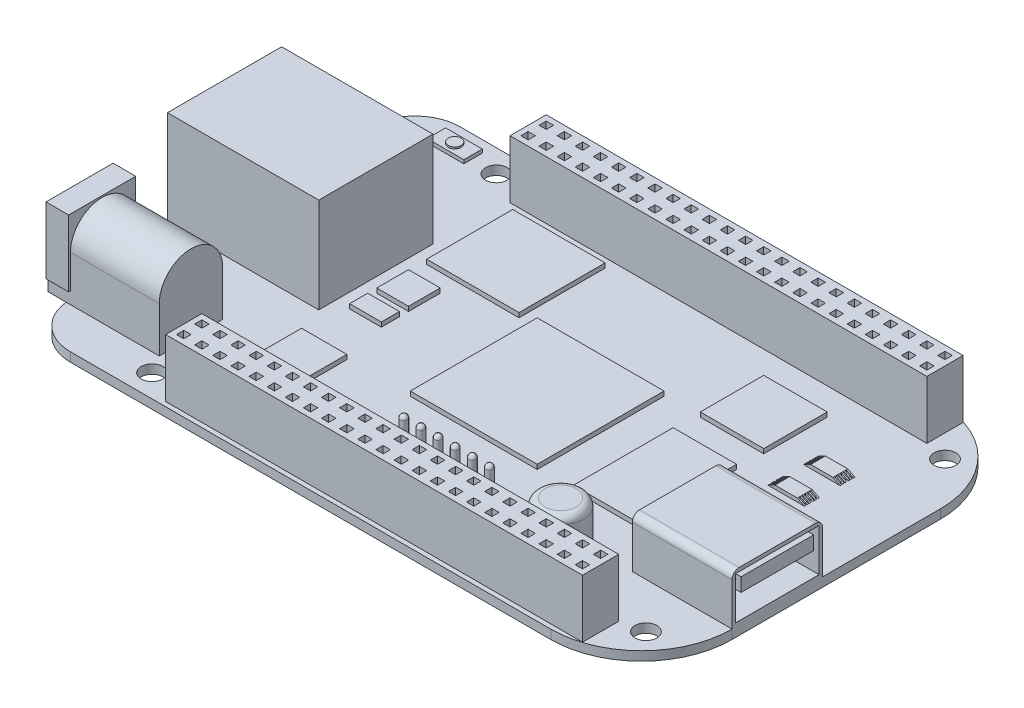
SolidWorks part; units mm, degrees
material "ABS"
ref_plane "Front Plane" through (0, 0, 0) normal (0, 0, 1) x (1, 0, 0)
ref_plane "Top Plane" through (0, 0, 0) normal (0, 1, 0) x (1, 0, 0)
ref_plane "Right Plane" through (0, 0, 0) normal (1, 0, 0) x (0, 0, -1)
sketch "Sketch1" plane through (0, 0, 0) normal (0, 1, 0) x (1, 0, 0)
  line L1 (-12.7, 0) -> (-80.01, 0)
  line L2 (0, 12.7) -> (0, 41.91)
  line L3 (-12.7, 54.61) -> (-80.01, 54.61)
  line L4 (-86.36, 6.35) -> (-86.36, 48.26)
  arc A0 (0, 12.7) -> (-12.7, 0) centre (-12.7, 12.7) cw
  arc A1 (0, 41.91) -> (-12.7, 54.61) centre (-12.7, 41.91) ccw
  arc A2 (-86.36, 6.35) -> (-80.01, 0) centre (-80.01, 6.35) ccw
  arc A3 (-86.36, 48.26) -> (-80.01, 54.61) centre (-80.01, 48.26) cw
  point P7 (0, 0)
  point P10 (0, 54.61)
  point P13 (-86.36, 0)
  dimension "D3" = 12.7
  dimension "D4" = 6.35
  dimension "D1" = 86.36
  dimension "D2" = 54.61
extrude "Boss-Extrude1" add sketch "Sketch1" along normal blind 1.27
sketch "Sketch2" plane through (0, 1.27, 0) normal (0, 1, 0) x (1, 0, 0)
  line L0 (-80.01, 0) -> (-12.7, 0) construction
  line L2 (-71.755, 51.435) -> (-71.755, 3.175) construction
  line L3 (-86.36, 48.26) -> (-86.36, 6.35) construction
  line L4 (-5.715, 48.26) -> (-5.715, 6.35) construction
  circle A0 centre (-71.755, 51.435) radius 1.524
  circle A1 centre (-71.755, 3.175) radius 1.524
  circle A2 centre (-5.715, 48.26) radius 1.524
  circle A3 centre (-5.715, 6.35) radius 1.524
  dimension "D7" = 3.048
  dimension "D1" = 48.26
  dimension "D2" = 41.91
  dimension "D3" = 6.35
  dimension "D4" = 14.605
  dimension "D5" = 80.645
  dimension "D6" = 3.175
extrude "Cut-Extrude1" cut sketch "Sketch2" along direction (0, -1, 0) on the side against the normal up to surface (1.27 mm away) up to face at (-44.4387, 0, -27.305)
sketch "Sketch3" plane through (0, 1.27, 0) normal (0, 1, 0) x (1, 0, 0)
  line L0 (-10.16, 48.895) -> (-10.16, 50.165) construction
  line L1 (-67.31, 53.975) -> (-8.89, 53.975)
  line L2 (-67.31, 53.975) -> (-67.31, 48.895)
  line L3 (-67.31, 48.895) -> (-8.89, 48.895)
  line L4 (-8.89, 53.975) -> (-8.89, 48.895)
  line L5 (-86.36, 27.305) -> (0, 27.305) construction
  line L6 (0, 12.7) -> (0, 41.91) construction
  line L7 (-66.548, 4.953) -> (-66.548, 3.937)
  line L8 (-66.548, 4.953) -> (-65.532, 4.953)
  line L9 (-10.16, 50.165) -> (-10.16, 52.705) construction
  line L10 (-10.16, 52.705) -> (-10.16, 53.975) construction
  line L11 (-13.208, 52.197) -> (-12.192, 52.197)
  line L12 (-10.668, 53.213) -> (-9.652, 53.213)
  line L13 (-10.668, 53.213) -> (-10.668, 52.197)
  line L14 (-10.668, 52.197) -> (-9.652, 52.197)
  line L15 (-9.652, 53.213) -> (-9.652, 52.197)
  line L16 (-10.668, 53.213) -> (-9.652, 52.197) construction
  line L17 (-10.668, 52.197) -> (-9.652, 53.213) construction
  line L18 (-10.668, 49.657) -> (-9.652, 49.657)
  line L19 (-10.668, 49.657) -> (-10.668, 50.673)
  line L20 (-10.668, 50.673) -> (-9.652, 50.673)
  line L21 (-9.652, 49.657) -> (-9.652, 50.673)
  line L22 (-10.668, 49.657) -> (-9.652, 50.673) construction
  line L23 (-10.668, 50.673) -> (-9.652, 49.657) construction
  line L24 (-13.208, 53.213) -> (-13.208, 52.197)
  line L25 (-13.208, 53.213) -> (-12.192, 53.213)
  line L26 (-12.192, 53.213) -> (-12.192, 52.197)
  line L27 (-13.208, 50.673) -> (-12.192, 50.673)
  line L28 (-12.192, 49.657) -> (-12.192, 50.673)
  line L29 (-13.208, 49.657) -> (-12.192, 49.657)
  line L30 (-13.208, 49.657) -> (-13.208, 50.673)
  line L31 (-15.748, 52.197) -> (-14.732, 52.197)
  line L32 (-15.748, 53.213) -> (-15.748, 52.197)
  line L33 (-15.748, 53.213) -> (-14.732, 53.213)
  line L34 (-14.732, 53.213) -> (-14.732, 52.197)
  line L35 (-15.748, 50.673) -> (-14.732, 50.673)
  line L36 (-14.732, 49.657) -> (-14.732, 50.673)
  line L37 (-15.748, 49.657) -> (-14.732, 49.657)
  line L38 (-15.748, 49.657) -> (-15.748, 50.673)
  line L39 (-18.288, 52.197) -> (-17.272, 52.197)
  line L40 (-18.288, 53.213) -> (-18.288, 52.197)
  line L41 (-18.288, 53.213) -> (-17.272, 53.213)
  line L42 (-17.272, 53.213) -> (-17.272, 52.197)
  line L43 (-18.288, 50.673) -> (-17.272, 50.673)
  line L44 (-17.272, 49.657) -> (-17.272, 50.673)
  line L45 (-18.288, 49.657) -> (-17.272, 49.657)
  line L46 (-18.288, 49.657) -> (-18.288, 50.673)
  line L47 (-20.828, 52.197) -> (-19.812, 52.197)
  line L48 (-20.828, 53.213) -> (-20.828, 52.197)
  line L49 (-20.828, 53.213) -> (-19.812, 53.213)
  line L50 (-19.812, 53.213) -> (-19.812, 52.197)
  line L51 (-20.828, 50.673) -> (-19.812, 50.673)
  line L52 (-19.812, 49.657) -> (-19.812, 50.673)
  line L53 (-20.828, 49.657) -> (-19.812, 49.657)
  line L54 (-20.828, 49.657) -> (-20.828, 50.673)
  line L55 (-23.368, 52.197) -> (-22.352, 52.197)
  line L56 (-23.368, 53.213) -> (-23.368, 52.197)
  line L57 (-23.368, 53.213) -> (-22.352, 53.213)
  line L58 (-22.352, 53.213) -> (-22.352, 52.197)
  line L59 (-23.368, 50.673) -> (-22.352, 50.673)
  line L60 (-22.352, 49.657) -> (-22.352, 50.673)
  line L61 (-23.368, 49.657) -> (-22.352, 49.657)
  line L62 (-23.368, 49.657) -> (-23.368, 50.673)
  line L63 (-25.908, 52.197) -> (-24.892, 52.197)
  line L64 (-25.908, 53.213) -> (-25.908, 52.197)
  line L65 (-25.908, 53.213) -> (-24.892, 53.213)
  line L66 (-24.892, 53.213) -> (-24.892, 52.197)
  line L67 (-25.908, 50.673) -> (-24.892, 50.673)
  line L68 (-24.892, 49.657) -> (-24.892, 50.673)
  line L69 (-25.908, 49.657) -> (-24.892, 49.657)
  line L70 (-25.908, 49.657) -> (-25.908, 50.673)
  line L71 (-28.448, 52.197) -> (-27.432, 52.197)
  line L72 (-28.448, 53.213) -> (-28.448, 52.197)
  line L73 (-28.448, 53.213) -> (-27.432, 53.213)
  line L74 (-27.432, 53.213) -> (-27.432, 52.197)
  line L75 (-28.448, 50.673) -> (-27.432, 50.673)
  line L76 (-27.432, 49.657) -> (-27.432, 50.673)
  line L77 (-28.448, 49.657) -> (-27.432, 49.657)
  line L78 (-28.448, 49.657) -> (-28.448, 50.673)
  line L79 (-30.988, 52.197) -> (-29.972, 52.197)
  line L80 (-30.988, 53.213) -> (-30.988, 52.197)
  line L81 (-30.988, 53.213) -> (-29.972, 53.213)
  line L82 (-29.972, 53.213) -> (-29.972, 52.197)
  line L83 (-30.988, 50.673) -> (-29.972, 50.673)
  line L84 (-29.972, 49.657) -> (-29.972, 50.673)
  line L85 (-30.988, 49.657) -> (-29.972, 49.657)
  line L86 (-30.988, 49.657) -> (-30.988, 50.673)
  line L87 (-33.528, 52.197) -> (-32.512, 52.197)
  line L88 (-33.528, 53.213) -> (-33.528, 52.197)
  line L89 (-33.528, 53.213) -> (-32.512, 53.213)
  line L90 (-32.512, 53.213) -> (-32.512, 52.197)
  line L91 (-33.528, 50.673) -> (-32.512, 50.673)
  line L92 (-32.512, 49.657) -> (-32.512, 50.673)
  line L93 (-33.528, 49.657) -> (-32.512, 49.657)
  line L94 (-33.528, 49.657) -> (-33.528, 50.673)
  line L95 (-36.068, 52.197) -> (-35.052, 52.197)
  line L96 (-36.068, 53.213) -> (-36.068, 52.197)
  line L97 (-36.068, 53.213) -> (-35.052, 53.213)
  line L98 (-35.052, 53.213) -> (-35.052, 52.197)
  line L99 (-36.068, 50.673) -> (-35.052, 50.673)
  line L100 (-35.052, 49.657) -> (-35.052, 50.673)
  line L101 (-36.068, 49.657) -> (-35.052, 49.657)
  line L102 (-36.068, 49.657) -> (-36.068, 50.673)
  line L103 (-38.608, 52.197) -> (-37.592, 52.197)
  line L104 (-38.608, 53.213) -> (-38.608, 52.197)
  line L105 (-38.608, 53.213) -> (-37.592, 53.213)
  line L106 (-37.592, 53.213) -> (-37.592, 52.197)
  line L107 (-38.608, 50.673) -> (-37.592, 50.673)
  line L108 (-37.592, 49.657) -> (-37.592, 50.673)
  line L109 (-38.608, 49.657) -> (-37.592, 49.657)
  line L110 (-38.608, 49.657) -> (-38.608, 50.673)
  line L111 (-41.148, 52.197) -> (-40.132, 52.197)
  line L112 (-41.148, 53.213) -> (-41.148, 52.197)
  line L113 (-41.148, 53.213) -> (-40.132, 53.213)
  line L114 (-40.132, 53.213) -> (-40.132, 52.197)
  line L115 (-41.148, 50.673) -> (-40.132, 50.673)
  line L116 (-40.132, 49.657) -> (-40.132, 50.673)
  line L117 (-41.148, 49.657) -> (-40.132, 49.657)
  line L118 (-41.148, 49.657) -> (-41.148, 50.673)
  line L119 (-43.688, 52.197) -> (-42.672, 52.197)
  line L120 (-43.688, 53.213) -> (-43.688, 52.197)
  line L121 (-43.688, 53.213) -> (-42.672, 53.213)
  line L122 (-42.672, 53.213) -> (-42.672, 52.197)
  line L123 (-43.688, 50.673) -> (-42.672, 50.673)
  line L124 (-42.672, 49.657) -> (-42.672, 50.673)
  line L125 (-43.688, 49.657) -> (-42.672, 49.657)
  line L126 (-43.688, 49.657) -> (-43.688, 50.673)
  line L127 (-46.228, 52.197) -> (-45.212, 52.197)
  line L128 (-46.228, 53.213) -> (-46.228, 52.197)
  line L129 (-46.228, 53.213) -> (-45.212, 53.213)
  line L130 (-45.212, 53.213) -> (-45.212, 52.197)
  line L131 (-46.228, 50.673) -> (-45.212, 50.673)
  line L132 (-45.212, 49.657) -> (-45.212, 50.673)
  line L133 (-46.228, 49.657) -> (-45.212, 49.657)
  line L134 (-46.228, 49.657) -> (-46.228, 50.673)
  line L135 (-48.768, 52.197) -> (-47.752, 52.197)
  line L136 (-48.768, 53.213) -> (-48.768, 52.197)
  line L137 (-48.768, 53.213) -> (-47.752, 53.213)
  line L138 (-47.752, 53.213) -> (-47.752, 52.197)
  line L139 (-48.768, 50.673) -> (-47.752, 50.673)
  line L140 (-47.752, 49.657) -> (-47.752, 50.673)
  line L141 (-48.768, 49.657) -> (-47.752, 49.657)
  line L142 (-48.768, 49.657) -> (-48.768, 50.673)
  line L143 (-51.308, 52.197) -> (-50.292, 52.197)
  line L144 (-51.308, 53.213) -> (-51.308, 52.197)
  line L145 (-51.308, 53.213) -> (-50.292, 53.213)
  line L146 (-50.292, 53.213) -> (-50.292, 52.197)
  line L147 (-51.308, 50.673) -> (-50.292, 50.673)
  line L148 (-50.292, 49.657) -> (-50.292, 50.673)
  line L149 (-51.308, 49.657) -> (-50.292, 49.657)
  line L150 (-51.308, 49.657) -> (-51.308, 50.673)
  line L151 (-53.848, 52.197) -> (-52.832, 52.197)
  line L152 (-53.848, 53.213) -> (-53.848, 52.197)
  line L153 (-53.848, 53.213) -> (-52.832, 53.213)
  line L154 (-52.832, 53.213) -> (-52.832, 52.197)
  line L155 (-53.848, 50.673) -> (-52.832, 50.673)
  line L156 (-52.832, 49.657) -> (-52.832, 50.673)
  line L157 (-53.848, 49.657) -> (-52.832, 49.657)
  line L158 (-53.848, 49.657) -> (-53.848, 50.673)
  line L159 (-56.388, 52.197) -> (-55.372, 52.197)
  line L160 (-56.388, 53.213) -> (-56.388, 52.197)
  line L161 (-56.388, 53.213) -> (-55.372, 53.213)
  line L162 (-55.372, 53.213) -> (-55.372, 52.197)
  line L163 (-56.388, 50.673) -> (-55.372, 50.673)
  line L164 (-55.372, 49.657) -> (-55.372, 50.673)
  line L165 (-56.388, 49.657) -> (-55.372, 49.657)
  line L166 (-56.388, 49.657) -> (-56.388, 50.673)
  line L167 (-58.928, 52.197) -> (-57.912, 52.197)
  line L168 (-58.928, 53.213) -> (-58.928, 52.197)
  line L169 (-58.928, 53.213) -> (-57.912, 53.213)
  line L170 (-57.912, 53.213) -> (-57.912, 52.197)
  line L171 (-58.928, 50.673) -> (-57.912, 50.673)
  line L172 (-57.912, 49.657) -> (-57.912, 50.673)
  line L173 (-58.928, 49.657) -> (-57.912, 49.657)
  line L174 (-58.928, 49.657) -> (-58.928, 50.673)
  line L175 (-61.468, 52.197) -> (-60.452, 52.197)
  line L176 (-61.468, 53.213) -> (-61.468, 52.197)
  line L177 (-61.468, 53.213) -> (-60.452, 53.213)
  line L178 (-60.452, 53.213) -> (-60.452, 52.197)
  line L179 (-61.468, 50.673) -> (-60.452, 50.673)
  line L180 (-60.452, 49.657) -> (-60.452, 50.673)
  line L181 (-61.468, 49.657) -> (-60.452, 49.657)
  line L182 (-61.468, 49.657) -> (-61.468, 50.673)
  line L183 (-64.008, 52.197) -> (-62.992, 52.197)
  line L184 (-64.008, 53.213) -> (-64.008, 52.197)
  line L185 (-64.008, 53.213) -> (-62.992, 53.213)
  line L186 (-62.992, 53.213) -> (-62.992, 52.197)
  line L187 (-64.008, 50.673) -> (-62.992, 50.673)
  line L188 (-62.992, 49.657) -> (-62.992, 50.673)
  line L189 (-64.008, 49.657) -> (-62.992, 49.657)
  line L190 (-64.008, 49.657) -> (-64.008, 50.673)
  line L191 (-66.548, 52.197) -> (-65.532, 52.197)
  line L192 (-66.548, 53.213) -> (-66.548, 52.197)
  line L193 (-66.548, 53.213) -> (-65.532, 53.213)
  line L194 (-65.532, 53.213) -> (-65.532, 52.197)
  line L195 (-66.548, 50.673) -> (-65.532, 50.673)
  line L196 (-65.532, 49.657) -> (-65.532, 50.673)
  line L197 (-66.548, 49.657) -> (-65.532, 49.657)
  line L198 (-66.548, 49.657) -> (-66.548, 50.673)
  line L199 (-66.548, 49.657) -> (-65.532, 50.673) construction
  line L200 (-86.36, 48.26) -> (-86.36, 6.35) construction
  line L201 (-65.532, 4.953) -> (-65.532, 3.937)
  line L202 (-12.7, 54.61) -> (-80.01, 54.61) construction
  line L203 (-66.548, 3.937) -> (-65.532, 3.937)
  line L204 (-65.532, 1.397) -> (-65.532, 2.413)
  line L205 (-66.548, 1.397) -> (-65.532, 1.397)
  line L206 (-66.548, 1.397) -> (-66.548, 2.413)
  line L207 (-66.548, 2.413) -> (-65.532, 2.413)
  line L208 (-64.008, 4.953) -> (-64.008, 3.937)
  line L209 (-64.008, 4.953) -> (-62.992, 4.953)
  line L210 (-62.992, 4.953) -> (-62.992, 3.937)
  line L211 (-64.008, 3.937) -> (-62.992, 3.937)
  line L212 (-62.992, 1.397) -> (-62.992, 2.413)
  line L213 (-64.008, 1.397) -> (-62.992, 1.397)
  line L214 (-64.008, 1.397) -> (-64.008, 2.413)
  line L215 (-64.008, 2.413) -> (-62.992, 2.413)
  line L216 (-61.468, 4.953) -> (-61.468, 3.937)
  line L217 (-61.468, 4.953) -> (-60.452, 4.953)
  line L218 (-60.452, 4.953) -> (-60.452, 3.937)
  line L219 (-61.468, 3.937) -> (-60.452, 3.937)
  line L220 (-60.452, 1.397) -> (-60.452, 2.413)
  line L221 (-61.468, 1.397) -> (-60.452, 1.397)
  line L222 (-61.468, 1.397) -> (-61.468, 2.413)
  line L223 (-61.468, 2.413) -> (-60.452, 2.413)
  line L224 (-58.928, 4.953) -> (-58.928, 3.937)
  line L225 (-58.928, 4.953) -> (-57.912, 4.953)
  line L226 (-57.912, 4.953) -> (-57.912, 3.937)
  line L227 (-58.928, 3.937) -> (-57.912, 3.937)
  line L228 (-57.912, 1.397) -> (-57.912, 2.413)
  line L229 (-58.928, 1.397) -> (-57.912, 1.397)
  line L230 (-58.928, 1.397) -> (-58.928, 2.413)
  line L231 (-58.928, 2.413) -> (-57.912, 2.413)
  line L232 (-56.388, 4.953) -> (-56.388, 3.937)
  line L233 (-56.388, 4.953) -> (-55.372, 4.953)
  line L234 (-55.372, 4.953) -> (-55.372, 3.937)
  line L235 (-56.388, 3.937) -> (-55.372, 3.937)
  line L236 (-55.372, 1.397) -> (-55.372, 2.413)
  line L237 (-56.388, 1.397) -> (-55.372, 1.397)
  line L238 (-56.388, 1.397) -> (-56.388, 2.413)
  line L239 (-56.388, 2.413) -> (-55.372, 2.413)
  line L240 (-53.848, 4.953) -> (-53.848, 3.937)
  line L241 (-53.848, 4.953) -> (-52.832, 4.953)
  line L242 (-52.832, 4.953) -> (-52.832, 3.937)
  line L243 (-53.848, 3.937) -> (-52.832, 3.937)
  line L244 (-52.832, 1.397) -> (-52.832, 2.413)
  line L245 (-53.848, 1.397) -> (-52.832, 1.397)
  line L246 (-53.848, 1.397) -> (-53.848, 2.413)
  line L247 (-53.848, 2.413) -> (-52.832, 2.413)
  line L248 (-51.308, 4.953) -> (-51.308, 3.937)
  line L249 (-51.308, 4.953) -> (-50.292, 4.953)
  line L250 (-50.292, 4.953) -> (-50.292, 3.937)
  line L251 (-51.308, 3.937) -> (-50.292, 3.937)
  line L252 (-50.292, 1.397) -> (-50.292, 2.413)
  line L253 (-51.308, 1.397) -> (-50.292, 1.397)
  line L254 (-51.308, 1.397) -> (-51.308, 2.413)
  line L255 (-51.308, 2.413) -> (-50.292, 2.413)
  line L256 (-48.768, 4.953) -> (-48.768, 3.937)
  line L257 (-48.768, 4.953) -> (-47.752, 4.953)
  line L258 (-47.752, 4.953) -> (-47.752, 3.937)
  line L259 (-48.768, 3.937) -> (-47.752, 3.937)
  line L260 (-47.752, 1.397) -> (-47.752, 2.413)
  line L261 (-48.768, 1.397) -> (-47.752, 1.397)
  line L262 (-48.768, 1.397) -> (-48.768, 2.413)
  line L263 (-48.768, 2.413) -> (-47.752, 2.413)
  line L264 (-46.228, 4.953) -> (-46.228, 3.937)
  line L265 (-46.228, 4.953) -> (-45.212, 4.953)
  line L266 (-45.212, 4.953) -> (-45.212, 3.937)
  line L267 (-46.228, 3.937) -> (-45.212, 3.937)
  line L268 (-45.212, 1.397) -> (-45.212, 2.413)
  line L269 (-46.228, 1.397) -> (-45.212, 1.397)
  line L270 (-46.228, 1.397) -> (-46.228, 2.413)
  line L271 (-46.228, 2.413) -> (-45.212, 2.413)
  line L272 (-43.688, 4.953) -> (-43.688, 3.937)
  line L273 (-43.688, 4.953) -> (-42.672, 4.953)
  line L274 (-42.672, 4.953) -> (-42.672, 3.937)
  line L275 (-43.688, 3.937) -> (-42.672, 3.937)
  line L276 (-42.672, 1.397) -> (-42.672, 2.413)
  line L277 (-43.688, 1.397) -> (-42.672, 1.397)
  line L278 (-43.688, 1.397) -> (-43.688, 2.413)
  line L279 (-43.688, 2.413) -> (-42.672, 2.413)
  line L280 (-41.148, 4.953) -> (-41.148, 3.937)
  line L281 (-41.148, 4.953) -> (-40.132, 4.953)
  line L282 (-40.132, 4.953) -> (-40.132, 3.937)
  line L283 (-41.148, 3.937) -> (-40.132, 3.937)
  line L284 (-40.132, 1.397) -> (-40.132, 2.413)
  line L285 (-41.148, 1.397) -> (-40.132, 1.397)
  line L286 (-41.148, 1.397) -> (-41.148, 2.413)
  line L287 (-41.148, 2.413) -> (-40.132, 2.413)
  line L288 (-38.608, 4.953) -> (-38.608, 3.937)
  line L289 (-38.608, 4.953) -> (-37.592, 4.953)
  line L290 (-37.592, 4.953) -> (-37.592, 3.937)
  line L291 (-38.608, 3.937) -> (-37.592, 3.937)
  line L292 (-37.592, 1.397) -> (-37.592, 2.413)
  line L293 (-38.608, 1.397) -> (-37.592, 1.397)
  line L294 (-38.608, 1.397) -> (-38.608, 2.413)
  line L295 (-38.608, 2.413) -> (-37.592, 2.413)
  line L296 (-36.068, 4.953) -> (-36.068, 3.937)
  line L297 (-36.068, 4.953) -> (-35.052, 4.953)
  line L298 (-35.052, 4.953) -> (-35.052, 3.937)
  line L299 (-36.068, 3.937) -> (-35.052, 3.937)
  line L300 (-35.052, 1.397) -> (-35.052, 2.413)
  line L301 (-36.068, 1.397) -> (-35.052, 1.397)
  line L302 (-36.068, 1.397) -> (-36.068, 2.413)
  line L303 (-36.068, 2.413) -> (-35.052, 2.413)
  line L304 (-33.528, 4.953) -> (-33.528, 3.937)
  line L305 (-33.528, 4.953) -> (-32.512, 4.953)
  line L306 (-32.512, 4.953) -> (-32.512, 3.937)
  line L307 (-33.528, 3.937) -> (-32.512, 3.937)
  line L308 (-32.512, 1.397) -> (-32.512, 2.413)
  line L309 (-33.528, 1.397) -> (-32.512, 1.397)
  line L310 (-33.528, 1.397) -> (-33.528, 2.413)
  line L311 (-33.528, 2.413) -> (-32.512, 2.413)
  line L312 (-30.988, 4.953) -> (-30.988, 3.937)
  line L313 (-30.988, 4.953) -> (-29.972, 4.953)
  line L314 (-29.972, 4.953) -> (-29.972, 3.937)
  line L315 (-30.988, 3.937) -> (-29.972, 3.937)
  line L316 (-29.972, 1.397) -> (-29.972, 2.413)
  line L317 (-30.988, 1.397) -> (-29.972, 1.397)
  line L318 (-30.988, 1.397) -> (-30.988, 2.413)
  line L319 (-30.988, 2.413) -> (-29.972, 2.413)
  line L320 (-28.448, 4.953) -> (-28.448, 3.937)
  line L321 (-28.448, 4.953) -> (-27.432, 4.953)
  line L322 (-27.432, 4.953) -> (-27.432, 3.937)
  line L323 (-28.448, 3.937) -> (-27.432, 3.937)
  line L324 (-27.432, 1.397) -> (-27.432, 2.413)
  line L325 (-28.448, 1.397) -> (-27.432, 1.397)
  line L326 (-28.448, 1.397) -> (-28.448, 2.413)
  line L327 (-28.448, 2.413) -> (-27.432, 2.413)
  line L328 (-25.908, 4.953) -> (-25.908, 3.937)
  line L329 (-25.908, 4.953) -> (-24.892, 4.953)
  line L330 (-24.892, 4.953) -> (-24.892, 3.937)
  line L331 (-25.908, 3.937) -> (-24.892, 3.937)
  line L332 (-24.892, 1.397) -> (-24.892, 2.413)
  line L333 (-25.908, 1.397) -> (-24.892, 1.397)
  line L334 (-25.908, 1.397) -> (-25.908, 2.413)
  line L335 (-25.908, 2.413) -> (-24.892, 2.413)
  line L336 (-23.368, 4.953) -> (-23.368, 3.937)
  line L337 (-23.368, 4.953) -> (-22.352, 4.953)
  line L338 (-22.352, 4.953) -> (-22.352, 3.937)
  line L339 (-23.368, 3.937) -> (-22.352, 3.937)
  line L340 (-22.352, 1.397) -> (-22.352, 2.413)
  line L341 (-23.368, 1.397) -> (-22.352, 1.397)
  line L342 (-23.368, 1.397) -> (-23.368, 2.413)
  line L343 (-23.368, 2.413) -> (-22.352, 2.413)
  line L344 (-20.828, 4.953) -> (-20.828, 3.937)
  line L345 (-20.828, 4.953) -> (-19.812, 4.953)
  line L346 (-19.812, 4.953) -> (-19.812, 3.937)
  line L347 (-20.828, 3.937) -> (-19.812, 3.937)
  line L348 (-19.812, 1.397) -> (-19.812, 2.413)
  line L349 (-20.828, 1.397) -> (-19.812, 1.397)
  line L350 (-20.828, 1.397) -> (-20.828, 2.413)
  line L351 (-20.828, 2.413) -> (-19.812, 2.413)
  line L352 (-18.288, 4.953) -> (-18.288, 3.937)
  line L353 (-18.288, 4.953) -> (-17.272, 4.953)
  line L354 (-17.272, 4.953) -> (-17.272, 3.937)
  line L355 (-18.288, 3.937) -> (-17.272, 3.937)
  line L356 (-17.272, 1.397) -> (-17.272, 2.413)
  line L357 (-18.288, 1.397) -> (-17.272, 1.397)
  line L358 (-18.288, 1.397) -> (-18.288, 2.413)
  line L359 (-18.288, 2.413) -> (-17.272, 2.413)
  line L360 (-15.748, 4.953) -> (-15.748, 3.937)
  line L361 (-15.748, 4.953) -> (-14.732, 4.953)
  line L362 (-14.732, 4.953) -> (-14.732, 3.937)
  line L363 (-15.748, 3.937) -> (-14.732, 3.937)
  line L364 (-14.732, 1.397) -> (-14.732, 2.413)
  line L365 (-15.748, 1.397) -> (-14.732, 1.397)
  line L366 (-15.748, 1.397) -> (-15.748, 2.413)
  line L367 (-15.748, 2.413) -> (-14.732, 2.413)
  line L368 (-13.208, 4.953) -> (-13.208, 3.937)
  line L369 (-13.208, 4.953) -> (-12.192, 4.953)
  line L370 (-12.192, 4.953) -> (-12.192, 3.937)
  line L371 (-13.208, 3.937) -> (-12.192, 3.937)
  line L372 (-12.192, 1.397) -> (-12.192, 2.413)
  line L373 (-13.208, 1.397) -> (-12.192, 1.397)
  line L374 (-13.208, 1.397) -> (-13.208, 2.413)
  line L375 (-9.652, 4.953) -> (-9.652, 3.937)
  line L376 (-10.668, 3.937) -> (-9.652, 3.937)
  line L377 (-10.668, 4.953) -> (-10.668, 3.937)
  line L378 (-10.668, 4.953) -> (-9.652, 4.953)
  line L379 (-9.652, 1.397) -> (-9.652, 2.413)
  line L380 (-10.668, 2.413) -> (-9.652, 2.413)
  line L381 (-10.668, 1.397) -> (-10.668, 2.413)
  line L382 (-10.668, 1.397) -> (-9.652, 1.397)
  line L383 (-13.208, 2.413) -> (-12.192, 2.413)
  line L384 (-8.89, 0.635) -> (-8.89, 5.715)
  line L385 (-67.31, 5.715) -> (-8.89, 5.715)
  line L386 (-67.31, 0.635) -> (-67.31, 5.715)
  line L387 (-67.31, 0.635) -> (-8.89, 0.635)
  circle A0 centre (-66.04, 50.165) radius 0.1361
  dimension "D1" = 1.016
  dimension "D2" = 2.54
  dimension "D3" = 5.08
  dimension "D4" = 58.42
  dimension "D5" = 1.27
  dimension "D7" = 20.32
  dimension "D8" = 0.635
  dimension "D6" = 23
extrude "Boss-Extrude2" add sketch "Sketch3" along normal blind 8.128 contours L4 L1 L2 L3 L193 L194 L191 L192 L185 L186 L183 L184 L177 L178 L175 L176 L169 L170 L167 L168 L161 L162 L159 L160 L153 L154 L151 L152 L145 L146 L143 L144 L137 L138 L135 L136 L129 L130 L127 L128 L121 | L386 L387 L384 L385 L374 L383 L372 L373 L382 L381 L380 L379 L366 L367 L364 L365 L363 L360 L361 L362 L350 L351 L348 L349 L347 L344 L345 L346 L334 L335 L332 L333 L331 L328 L329 L330 L318 L319 L316 L317 L315 region at (-38.1, 1.27, -51.435) region at (-38.1, 1.27, -3.175)
sketch "Sketch4" plane through (0, 1.27, 0) normal (0, 1, 0) x (1, 0, 0)
  line L0 (-86.36, 48.26) -> (-86.36, 6.35) construction
  line L1 (-67.691, 22.479) -> (-88.9, 22.479)
  line L2 (-67.691, 22.479) -> (-67.691, 38.481)
  line L3 (-67.691, 38.481) -> (-88.9, 38.481)
  line L4 (-88.9, 22.479) -> (-88.9, 38.481)
  line L5 (-12.7, 54.61) -> (-80.01, 54.61) construction
  dimension "D1" = 2.54
  dimension "D2" = 21.209
  dimension "D3" = 16.002
  dimension "D4" = 16.129
extrude "Boss-Extrude3" add sketch "Sketch4" along normal blind 13.335
sketch "Sketch5" plane through (-88.9, 0, 0) normal (-1, 0, 0) x (0, 0, 1)
  line L0 (-30.48, 2.286) -> (-30.48, 3.937) construction
  line L1 (-36.83, 12.065) -> (-24.13, 12.065)
  line L2 (-36.83, 12.065) -> (-36.83, 5.461)
  line L3 (-36.83, 5.461) -> (-24.13, 5.461)
  line L4 (-24.13, 12.065) -> (-24.13, 5.461)
  line L5 (-33.655, 5.461) -> (-27.305, 5.461)
  line L6 (-33.655, 5.461) -> (-33.655, 3.937)
  line L7 (-33.655, 3.937) -> (-27.305, 3.937)
  line L8 (-27.305, 5.461) -> (-27.305, 3.937)
  line L9 (-32.512, 3.937) -> (-28.448, 3.937)
  line L10 (-32.512, 3.937) -> (-32.512, 2.286)
  line L11 (-32.512, 2.286) -> (-28.448, 2.286)
  line L12 (-28.448, 3.937) -> (-28.448, 2.286)
  line L13 (-30.48, 3.937) -> (-30.48, 5.461) construction
  line L14 (-38.481, 14.605) -> (-22.479, 14.605) construction
  line L15 (-36.83, 12.065) -> (-38.481, 12.065) construction
  line L16 (-38.481, 14.605) -> (-38.481, 1.27) construction
  line L17 (-24.13, 12.065) -> (-22.479, 12.065) construction
  line L18 (-22.479, 14.605) -> (-22.479, 1.27) construction
  dimension "D1" = 12.7
  dimension "D2" = 6.604
  dimension "D3" = 2.54
  dimension "D4" = 1.524
  dimension "D5" = 1.651
  dimension "D6" = 4.064
  dimension "D7" = 6.35
extrude "Cut-Extrude2" cut sketch "Sketch5" against normal blind 17.78 contours L4 L1 L2 L3 | L8 L3 L6 L7 | L12 L7 L10 L11 region at (-88.9, 8.763, -30.48) region at (-88.9, 4.699, -30.48) region at (-88.9, 3.1115, -30.48)
sketch "Sketch6" plane through (0, 1.27, 0) normal (0, 1, 0) x (1, 0, 0)
  line L0 (-67.31, 48.895) -> (-8.89, 48.895) construction
  line L1 (-65.659, 35.56) -> (-52.705, 35.56)
  line L2 (-65.659, 35.56) -> (-65.659, 47.625)
  line L3 (-65.659, 47.625) -> (-52.705, 47.625)
  line L4 (-52.705, 35.56) -> (-52.705, 47.625)
  line L5 (-50.8, 36.195) -> (-33.02, 36.195)
  line L6 (-50.8, 36.195) -> (-50.8, 18.415)
  line L7 (-50.8, 18.415) -> (-33.02, 18.415)
  line L8 (-33.02, 36.195) -> (-33.02, 18.415)
  line L9 (-27.94, 45.085) -> (-19.05, 45.085)
  line L10 (-27.94, 45.085) -> (-27.94, 36.195)
  line L11 (-27.94, 36.195) -> (-19.05, 36.195)
  line L12 (-19.05, 45.085) -> (-19.05, 36.195)
  line L13 (-27.94, 32.385) -> (-19.05, 32.385)
  line L14 (-27.94, 32.385) -> (-27.94, 18.415)
  line L15 (-27.94, 18.415) -> (-19.05, 18.415)
  line L16 (-19.05, 32.385) -> (-19.05, 18.415)
  line L17 (-66.04, 18.415) -> (-59.69, 18.415)
  line L18 (-66.04, 18.415) -> (-66.04, 12.065)
  line L19 (-66.04, 12.065) -> (-59.69, 12.065)
  line L20 (-59.69, 18.415) -> (-59.69, 12.065)
  line L21 (-65.659, 27.305) -> (-61.214, 27.305)
  line L22 (-65.659, 27.305) -> (-65.659, 24.765)
  line L23 (-65.659, 24.765) -> (-61.214, 24.765)
  line L24 (-61.214, 27.305) -> (-61.214, 24.765)
  line L25 (-65.659, 33.02) -> (-61.214, 33.02)
  line L26 (-65.659, 33.02) -> (-65.659, 28.575)
  line L27 (-65.659, 28.575) -> (-61.214, 28.575)
  line L28 (-61.214, 33.02) -> (-61.214, 28.575)
  line L29 (0, 12.7) -> (0, 41.91) construction
  line L30 (-67.31, 48.895) -> (-8.89, 48.895) construction
  line L31 (-67.31, 5.715) -> (-8.89, 5.715) construction
  line L33 (-67.31, 0.635) -> (-67.31, 5.715) construction
  dimension "D1" = 8.89
  dimension "D2" = 13.97
  dimension "D3" = 3.81
  dimension "D4" = 3.81
  dimension "D5" = 19.05
  dimension "D6" = 17.78
  dimension "D7" = 12.7
  dimension "D8" = 33.02
  dimension "D9" = 12.954
  dimension "D10" = 12.065
  dimension "D11" = 1.905
  dimension "D12" = 4.445
  dimension "D13" = 2.54
  dimension "D14" = 1.27
  dimension "D15" = 2.54
  dimension "D16" = 1.27
  dimension "D17" = 6.35
  dimension "D18" = 6.35
  dimension "D19" = 1.27
extrude "Boss-Extrude4" add sketch "Sketch6" along normal blind 0.635
sketch "Sketch7" plane through (0, 1.27, 0) normal (0, 1, 0) x (1, 0, 0)
  line L1 (0, 12.7) -> (-13.97, 12.7)
  line L2 (0, 12.7) -> (0, 25.4)
  line L3 (0, 25.4) -> (-13.97, 25.4)
  line L4 (-13.97, 12.7) -> (-13.97, 25.4)
  line L5 (-80.01, 0) -> (-12.7, 0) construction
  line L6 (0, 12.7) -> (0, 41.91) construction
  dimension "D1" = 12.7
  dimension "D2" = 13.97
  dimension "D3" = 25.4
extrude "Boss-Extrude5" add sketch "Sketch7" along normal blind 6.985
sketch "Sketch8" plane through (0, 0, 0) normal (1, 0, 0) x (0, 0, -1)
  line L0 (12.7, 8.255) -> (25.4, 8.255) construction
  line L1 (13.97, 6.985) -> (24.13, 6.985)
  line L2 (13.97, 6.985) -> (13.97, 5.08)
  line L3 (13.97, 5.08) -> (24.13, 5.08)
  line L4 (24.13, 6.985) -> (24.13, 5.08)
  line L5 (13.208, 7.747) -> (24.892, 7.747)
  line L6 (13.208, 7.747) -> (13.208, 1.778)
  line L7 (13.208, 1.778) -> (24.892, 1.778)
  line L8 (24.892, 7.747) -> (24.892, 1.778)
  line L9 (25.4, 8.255) -> (25.4, 1.27) construction
  line L10 (12.7, 8.255) -> (12.7, 1.27) construction
  line L11 (12.7, 1.27) -> (0, 1.27) construction
  line L12 (13.97, 7.18) -> (13.208, 7.18) construction
  line L14 (24.892, 6.9479) -> (24.13, 6.9479) construction
  dimension "D1" = 0.508
  dimension "D2" = 0.508
  dimension "D3" = 0.508
  dimension "D4" = 0.508
  dimension "D5" = 1.905
  dimension "D6" = 10.16
  dimension "D7" = 3.175
extrude "Cut-Extrude3" cut sketch "Sketch8" against normal blind 12.7
sketch "Sketch9" plane through (0, 1.27, 0) normal (0, 1, 0) x (1, 0, 0)
  line L0 (-88.9, 38.481) -> (-88.9, 22.479) construction
  line L1 (-73.279, 5.715) -> (-88.9, 5.715)
  line L2 (-73.279, 5.715) -> (-73.279, 14.605)
  line L3 (-73.279, 14.605) -> (-88.9, 14.605)
  line L4 (-88.9, 5.715) -> (-88.9, 14.605)
  line L5 (-67.31, 5.715) -> (-8.89, 5.715) construction
  circle A0 centre (-71.755, 3.175) radius 1.524 construction
  dimension "D1" = 8.89
extrude "Boss-Extrude6" add sketch "Sketch9" along normal blind 6.35
sketch "Sketch10" plane through (-88.9, 0, 0) normal (-1, 0, 0) x (0, 0, 1)
  line L0 (-14.605, 7.62) -> (-5.715, 7.62) construction
  circle A0 centre (-10.16, 7.62) radius 4.445
  circle A1 centre (-10.16, 7.62) radius 3.4925
  circle A2 centre (-10.16, 7.62) radius 0.635
  line M3 (-5.715, 7.62) -> (-14.605, 7.62)
  dimension "D1" = 1.27
  dimension "D2" = 6.985
extrude "Boss-Extrude7" add sketch "Sketch10" along direction (1, 0, 0) on the side against the normal up to surface (15.621 mm away) contours A1 A0 M3 | A1 A0 M3 | A2 M3 | A2 A1 M3 region at (-88.9, 7.7194, -6.1912) region at (-88.9, 3.2744, -10.16) region at (-88.9, 9.1437, -10.16) region at (-88.9, 7.8895, -10.16) up to face at (-73.279, 4.445, -10.16)
sketch "Sketch11" plane through (-88.9, 0, 0) normal (-1, 0, 0) x (0, 0, 1)
  line L0 (-14.605, 7.62) -> (-14.605, 1.27) construction
  line L1 (-5.461, 2.952) -> (-14.859, 2.952)
  line L2 (-5.461, 2.952) -> (-5.461, 12.288)
  line L3 (-5.461, 12.288) -> (-14.859, 12.288)
  line L4 (-14.859, 2.952) -> (-14.859, 12.288)
  line L5 (-5.461, 2.952) -> (-14.859, 12.288) construction
  line L6 (-5.461, 12.288) -> (-14.859, 2.952) construction
  point P0 (-10.16, 7.62)
  dimension "D1" = 0.254
extrude "Boss-Extrude8" add sketch "Sketch11" against normal blind 3.175
extrude "Cut-Extrude4" cut sketch "Sketch10<3>" against normal blind 12.7 contours A2 A1 M3 | A2 A1 M3 region at (-88.9, 9.1437, -10.16) region at (-88.9, 6.0963, -10.16)
sketch "Sketch10<3>" plane through (-88.9, 0, 0) normal (-1, 0, 0) x (0, 0, 1) same geometry as "Sketch10"
fillet "Fillet1" radius 0.635 1 edges at (-88.9, 7.62, -9.525)
sketch "Sketch13" plane through (0, 1.27, 0) normal (0, 1, 0) x (1, 0, 0)
  line L0 (-85.1081, 45.625) -> (-85.1081, 44.3766)
  line L1 (-80.4022, 50.3766) -> (-80.4022, 52.967)
  line L2 (-80.4022, 40.3766) -> (-75.2569, 40.3766)
  line L3 (-80.4022, 40.3766) -> (-80.4022, 42.967)
  line L4 (-80.4022, 42.967) -> (-75.2569, 42.967)
  line L5 (-85.1081, 47.625) -> (-81.6152, 47.625)
  line L6 (-85.1081, 47.625) -> (-85.1081, 46.3766)
  line L7 (-85.1081, 46.3766) -> (-81.6152, 46.3766)
  line L8 (-81.6152, 47.625) -> (-81.6152, 46.3766)
  line L9 (-85.1081, 45.625) -> (-81.6152, 45.625)
  line L10 (-81.6152, 45.625) -> (-81.6152, 44.3766)
  line L11 (-85.1081, 44.3766) -> (-81.6152, 44.3766)
  line L12 (-85.1081, 43.625) -> (-85.1081, 42.3766)
  line L13 (-85.1081, 43.625) -> (-81.6152, 43.625)
  line L14 (-81.6152, 43.625) -> (-81.6152, 42.3766)
  line L15 (-85.1081, 42.3766) -> (-81.6152, 42.3766)
  line L16 (-85.1081, 41.625) -> (-85.1081, 40.3766)
  line L17 (-85.1081, 41.625) -> (-81.6152, 41.625)
  line L18 (-81.6152, 41.625) -> (-81.6152, 40.3766)
  line L19 (-85.1081, 40.3766) -> (-81.6152, 40.3766)
  line L20 (-75.2569, 40.3766) -> (-75.2569, 42.967)
  line L21 (-80.4022, 50.3766) -> (-75.2569, 50.3766)
  line L22 (-75.2569, 50.3766) -> (-75.2569, 52.967)
  line L23 (-80.4022, 52.967) -> (-75.2569, 52.967)
  line L24 (-9.8278, 38.5983) -> (-9.8278, 38.3983)
  line L25 (-9.8278, 34.5526) -> (-9.8278, 34.7526)
  line L26 (-10.8276, 33.5983) -> (-9.8278, 33.5983)
  line L27 (-10.8276, 33.5983) -> (-10.8276, 33.3983)
  line L28 (-10.8276, 33.3983) -> (-9.8278, 33.3983)
  line L29 (-13.97, 34.7526) -> (-10.8276, 34.7526)
  line L30 (-13.97, 34.7526) -> (-13.97, 32.6861)
  line L31 (-13.97, 32.6861) -> (-10.8276, 32.6861)
  line L32 (-10.8276, 34.7526) -> (-10.8276, 32.6861)
  line L33 (-10.8276, 39.1779) -> (-9.8278, 39.1779)
  line L34 (-10.8276, 38.8404) -> (-9.8278, 38.8404)
  line L35 (-13.97, 38.3983) -> (-14.9698, 38.3983)
  line L36 (-10.8276, 39.7526) -> (-10.8276, 37.6861)
  line L37 (-9.8278, 33.5983) -> (-9.8278, 33.3983)
  line L38 (-10.8276, 33.2607) -> (-9.8278, 33.2607)
  line L39 (-10.8276, 33.2607) -> (-10.8276, 33.0607)
  line L40 (-10.8276, 33.0607) -> (-9.8278, 33.0607)
  line L41 (-9.8278, 33.2607) -> (-9.8278, 33.0607)
  line L42 (-10.8276, 32.8861) -> (-9.8278, 32.8861)
  line L43 (-10.8276, 32.8861) -> (-10.8276, 32.6861)
  line L44 (-10.8276, 32.6861) -> (-9.8278, 32.6861)
  line L45 (-9.8278, 32.8861) -> (-9.8278, 32.6861)
  line L46 (-10.8276, 34.7526) -> (-9.8278, 34.7526)
  line L47 (-10.8276, 34.5526) -> (-10.8276, 34.7526)
  line L48 (-10.8276, 34.5526) -> (-9.8278, 34.5526)
  line L49 (-9.8278, 34.1779) -> (-9.8278, 34.3779)
  line L50 (-10.8276, 34.3779) -> (-9.8278, 34.3779)
  line L51 (-10.8276, 34.1779) -> (-10.8276, 34.3779)
  line L52 (-10.8276, 34.1779) -> (-9.8278, 34.1779)
  line L53 (-9.8278, 33.8404) -> (-9.8278, 34.0404)
  line L54 (-10.8276, 34.0404) -> (-9.8278, 34.0404)
  line L55 (-10.8276, 33.8404) -> (-10.8276, 34.0404)
  line L56 (-10.8276, 33.8404) -> (-9.8278, 33.8404)
  line L57 (-10.8276, 39.5526) -> (-9.8278, 39.5526)
  line L58 (-13.97, 33.8404) -> (-14.9698, 33.8404)
  line L59 (-13.97, 33.8404) -> (-13.97, 34.0404)
  line L60 (-13.97, 34.0404) -> (-14.9698, 34.0404)
  line L61 (-14.9698, 33.8404) -> (-14.9698, 34.0404)
  line L62 (-13.97, 34.1779) -> (-14.9698, 34.1779)
  line L63 (-13.97, 34.1779) -> (-13.97, 34.3779)
  line L64 (-13.97, 34.3779) -> (-14.9698, 34.3779)
  line L65 (-14.9698, 34.1779) -> (-14.9698, 34.3779)
  line L66 (-13.97, 34.5526) -> (-14.9698, 34.5526)
  line L67 (-13.97, 34.5526) -> (-13.97, 34.7526)
  line L68 (-13.97, 34.7526) -> (-14.9698, 34.7526)
  line L69 (-14.9698, 32.8861) -> (-14.9698, 32.6861)
  line L70 (-13.97, 32.6861) -> (-14.9698, 32.6861)
  line L71 (-13.97, 32.8861) -> (-13.97, 32.6861)
  line L72 (-13.97, 32.8861) -> (-14.9698, 32.8861)
  line L73 (-14.9698, 33.2607) -> (-14.9698, 33.0607)
  line L74 (-13.97, 33.0607) -> (-14.9698, 33.0607)
  line L75 (-13.97, 33.2607) -> (-13.97, 33.0607)
  line L76 (-13.97, 33.2607) -> (-14.9698, 33.2607)
  line L77 (-14.9698, 33.5983) -> (-14.9698, 33.3983)
  line L78 (-13.97, 34.7526) -> (-13.97, 32.6861)
  line L79 (-13.97, 33.3983) -> (-14.9698, 33.3983)
  line L80 (-13.97, 33.5983) -> (-13.97, 33.3983)
  line L81 (-13.97, 33.5983) -> (-14.9698, 33.5983)
  line L82 (-14.9698, 34.5526) -> (-14.9698, 34.7526)
  line L83 (-13.97, 39.3779) -> (-14.9698, 39.3779)
  line L84 (-14.9698, 37.8861) -> (-14.9698, 37.6861)
  line L85 (-10.8276, 37.8861) -> (-9.8278, 37.8861)
  line L86 (-10.8276, 39.1779) -> (-10.8276, 39.3779)
  line L87 (-13.97, 38.2607) -> (-14.9698, 38.2607)
  line L88 (-14.9698, 38.8404) -> (-14.9698, 39.0404)
  line L89 (-14.9698, 39.5526) -> (-14.9698, 39.7526)
  line L90 (-9.8278, 37.8861) -> (-9.8278, 37.6861)
  line L91 (-13.97, 39.7526) -> (-14.9698, 39.7526)
  line L92 (-14.9698, 38.2607) -> (-14.9698, 38.0607)
  line L93 (-10.8276, 38.3983) -> (-9.8278, 38.3983)
  line L94 (-13.97, 38.8404) -> (-14.9698, 38.8404)
  line L95 (-13.97, 38.5983) -> (-13.97, 38.3983)
  line L96 (-10.8276, 38.5983) -> (-10.8276, 38.3983)
  line L97 (-14.9698, 39.1779) -> (-14.9698, 39.3779)
  line L98 (-13.97, 37.6861) -> (-14.9698, 37.6861)
  line L99 (-13.97, 39.7526) -> (-10.8276, 39.7526)
  line L100 (-10.8276, 38.2607) -> (-10.8276, 38.0607)
  line L101 (-9.8278, 38.2607) -> (-9.8278, 38.0607)
  line L102 (-14.9698, 38.5983) -> (-14.9698, 38.3983)
  line L103 (-9.8278, 39.5526) -> (-9.8278, 39.7526)
  line L104 (-13.97, 39.1779) -> (-14.9698, 39.1779)
  line L105 (-13.97, 37.6861) -> (-10.8276, 37.6861)
  line L106 (-10.8276, 39.7526) -> (-9.8278, 39.7526)
  line L107 (-13.97, 38.0607) -> (-14.9698, 38.0607)
  line L108 (-9.8278, 38.8404) -> (-9.8278, 39.0404)
  line L109 (-13.97, 38.8404) -> (-13.97, 39.0404)
  line L110 (-13.97, 38.5983) -> (-14.9698, 38.5983)
  line L111 (-13.97, 39.7526) -> (-13.97, 37.6861)
  line L112 (-10.8276, 39.5526) -> (-10.8276, 39.7526)
  line L113 (-13.97, 39.5526) -> (-14.9698, 39.5526)
  line L114 (-13.97, 37.8861) -> (-13.97, 37.6861)
  line L115 (-10.8276, 38.2607) -> (-9.8278, 38.2607)
  line L116 (-10.8276, 38.0607) -> (-9.8278, 38.0607)
  line L117 (-10.8276, 39.3779) -> (-9.8278, 39.3779)
  line L118 (-10.8276, 38.8404) -> (-10.8276, 39.0404)
  line L119 (-13.97, 39.7526) -> (-13.97, 37.6861)
  line L120 (-10.8276, 38.5983) -> (-9.8278, 38.5983)
  line L121 (-13.97, 39.1779) -> (-13.97, 39.3779)
  line L122 (-10.8276, 37.8861) -> (-10.8276, 37.6861)
  line L123 (-9.8278, 39.1779) -> (-9.8278, 39.3779)
  line L124 (-10.8276, 39.0404) -> (-9.8278, 39.0404)
  line L125 (-13.97, 38.2607) -> (-13.97, 38.0607)
  line L126 (-13.97, 39.0404) -> (-14.9698, 39.0404)
  line L127 (-10.8276, 37.6861) -> (-9.8278, 37.6861)
  line L128 (-13.97, 39.5526) -> (-13.97, 39.7526)
  line L129 (-13.97, 37.8861) -> (-14.9698, 37.8861)
  dimension "D1" = 4
  dimension "D2" = 2
extrude "Boss-Extrude9" add sketch "Sketch13" along normal blind 0.5 contours L23 L1 L21 L22 | L16 L19 L18 L17 | L12 L15 L14 L13 | L0 L11 L10 L9 | L8 L5 L6 L7 | L2 L20 L4 L3 | L99 L111 L109 L95 L105 L36 | L113 L111 L91 L89 | L95 L110 L102 L35 | L111 L129 L84 L98 | L36 L127 L90 L85 | L120 L36 L93 L24 | L33 L123 L117 L36 | L106 L36 L57 L103 | L30 L72 L69 L70 | L30 L76 L73 L74 | L32 L29 L30 L78 L31 L27 | L45 L42 L32 L44 | L41 L38 L32 L40 | L37 L26 L27 L28 | L32 L56 L53 L54 | L32 L52 L49 L50 | L32 L48 L25 L46 | L4 L20 L2 L3 | L9 L10 L11 L0 | L7 L8 L5 L6 | L83 L97 L104 L121 | L126 L88 L94 L109 | L87 L92 L107 L125 | L116 L101 L115 L100 | L124 L108 L34 L118 | L79 L77 L81 L80 | L60 L61 L58 L59 | L62 L65 L64 L63 | L67 L66 L82 L68 region at (-83.3617, 1.27, -45.0008) region at (-77.8296, 1.27, -51.6718) region at (-77.8296, 1.27, -41.6718) region at (-83.3617, 1.27, -47.0008) region at (-83.3617, 1.27, -43.0008) region at (-83.3617, 1.27, -41.0008) region at (-10.3277, 1.27, -38.4983) region at (-12.3988, 1.27, -38.7193) region at (-10.3277, 1.27, -39.2779) region at (-10.3277, 1.27, -37.7861) region at (-10.3277, 1.27, -39.6526) region at (-14.4699, 1.27, -37.7861) region at (-14.4699, 1.27, -39.6526) region at (-14.4699, 1.27, -38.4983) region at (-10.3277, 1.27, -34.6526) region at (-12.3988, 1.27, -33.7193) region at (-10.3277, 1.27, -34.2779) region at (-10.3277, 1.27, -33.9404) region at (-10.3277, 1.27, -33.4983) region at (-10.3277, 1.27, -33.1607) region at (-10.3277, 1.27, -32.7861) region at (-14.4699, 1.27, -33.1607) region at (-14.4699, 1.27, -32.7861)
chamfer "Chamfer1" distance 0.5 distance2 1 2 edges at (-14.9698, 1.77, -39.6526) (-9.8278, 1.77, -39.6526) first distance on face at (-14.9698, 1.52, -39.6526) first distance on face at (-9.8278, 1.52, -39.6526)
chamfer "Chamfer2" distance 0.5 distance2 1 2 edges at (-9.8278, 1.77, -32.7861) (-14.9698, 1.77, -32.7861) first distance on face at (-9.8278, 1.52, -32.7861) first distance on face at (-14.9698, 1.52, -32.7861)
sketch "Sketch14" plane through (0, 1.77, 0) normal (0, 1, 0) x (1, 0, 0)
  line L0 (-84.3639, 45.2638) -> (-84.3639, 44.8063)
  line L1 (-84.3639, 47.2638) -> (-82.305, 47.2638)
  line L2 (-84.3639, 47.2638) -> (-84.3639, 46.8063)
  line L3 (-84.3639, 46.8063) -> (-82.305, 46.8063)
  line L4 (-82.305, 47.2638) -> (-82.305, 46.8063)
  line L5 (-84.3639, 45.2638) -> (-82.305, 45.2638)
  line L6 (-82.305, 45.2638) -> (-82.305, 44.8063)
  line L7 (-84.3639, 44.8063) -> (-82.305, 44.8063)
  line L8 (-84.3639, 43.2638) -> (-84.3639, 42.8063)
  line L9 (-84.3639, 43.2638) -> (-82.305, 43.2638)
  line L10 (-82.305, 43.2638) -> (-82.305, 42.8063)
  line L11 (-84.3639, 42.8063) -> (-82.305, 42.8063)
  line L12 (-84.3639, 41.2638) -> (-84.3639, 40.8063)
  line L13 (-84.3639, 41.2638) -> (-82.305, 41.2638)
  line L14 (-82.305, 41.2638) -> (-82.305, 40.8063)
  line L15 (-84.3639, 40.8063) -> (-82.305, 40.8063)
  circle A0 centre (-77.8296, 51.6718) radius 0.9
  circle A1 centre (-77.8296, 41.6718) radius 0.9
  dimension "D1" = 4
extrude "Boss-Extrude10" add sketch "Sketch14" along normal blind 0.25
fillet "Fillet2" radius 1 2 edges at (-6.985, 8.255, -12.7) (-6.985, 8.255, -25.4)
sketch "Sketch15" plane through (0, 1.27, 0) normal (0, 1, 0) x (1, 0, 0)
  line L1 (-27.5112, 6.4431) -> (-41.5112, 6.4431)
  line L2 (-27.5112, 6.4431) -> (-27.5112, 8.2431)
  line L3 (-27.5112, 8.2431) -> (-41.5112, 8.2431)
  line L4 (-41.5112, 6.4431) -> (-41.5112, 8.2431)
extrude "Boss-Extrude11" add sketch "Sketch15" along normal blind 1
sketch "Sketch16" plane through (0, 2.27, 0) normal (0, 1, 0) x (1, 0, 0)
  circle A0 centre (-40.64, 7.3431) radius 0.5
  circle A1 centre (-38.24, 7.3431) radius 0.5
  circle A2 centre (-35.84, 7.3431) radius 0.5
  circle A3 centre (-33.44, 7.3431) radius 0.5
  circle A4 centre (-31.04, 7.3431) radius 0.5
  circle A5 centre (-28.64, 7.3431) radius 0.5
  dimension "D1" = 6
extrude "Boss-Extrude12" add sketch "Sketch16" along normal blind 7.5
fillet "Fillet3" radius 0.5 6 edges at (-40.64, 9.77, -6.8431) (-38.24, 9.77, -6.8431) (-35.84, 9.77, -6.8431) (-33.44, 9.77, -6.8431) (-31.04, 9.77, -6.8431) (-28.64, 9.77, -6.8431)
sketch "Sketch17" plane through (0, 1.27, 0) normal (0, 1, 0) x (1, 0, 0)
  circle A0 centre (-21.7424, 10.4145) radius 3.2
extrude "Boss-Extrude13" add sketch "Sketch17" along normal blind 6.2
fillet "Fillet4" radius 1 1 edges at (-21.7424, 7.47, -7.2145)
